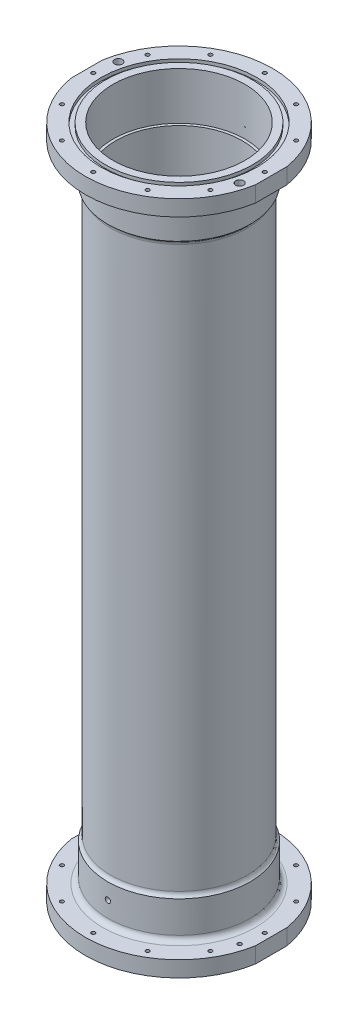
SolidWorks part; units mm, degrees
material "6061-T6 (SS)"
ref_plane "Front Plane" through (0, 0, 0) normal (0, 0, 1) x (1, 0, 0)
ref_plane "Top Plane" through (0, 0, 0) normal (0, 1, 0) x (1, 0, 0)
ref_plane "Right Plane" through (0, 0, 0) normal (1, 0, 0) x (0, 0, -1)
sketch "Sketch2" plane through (0, 0, 0) normal (0, 1, 0) x (1, 0, 0)
  circle A0 centre (0, 0) radius 38.1
  circle A1 centre (0, 0) radius 41.275
  dimension "D1" = 82.55
  dimension "D2" = 76.2
extrude "Base Cylinder" add sketch "Sketch2" along normal blind 406.4
sketch "Sketch3" plane through (0, 0, 0) normal (0, -1, 0) x (1, 0, 0)
  circle A0 centre (0, 0) radius 38.1
  circle A1 centre (0, 0) radius 56.3562
  dimension "D1" = 112.7125
extrude "Aft Flange" add sketch "Sketch3" against normal blind 9.525
sketch "Sketch34" plane through (0, 0, 0) normal (0, -1, 0) x (1, 0, 0)
  circle A0 centre (0, 0) radius 39.75
  dimension "D1" = 79.5
extrude "TemperatureInsert" cut sketch "Sketch34" against normal blind 28.575
sketch "Sketch6" plane through (0, 0, 0) normal (0, -1, 0) x (1, 0, 0)
  circle A0 centre (0, 0) radius 46.9011
  circle A1 centre (0, 0) radius 44.2849
  dimension "D1" = 93.8022
  dimension "D2" = 88.5698
extrude "Aft O-Ring" cut sketch "Sketch6" against normal blind 1.9812
sketch "Sketch33" plane through (0, 9.525, 0) normal (0, 1, 0) x (1, 0, 0)
  circle A0 centre (0, 0) radius 41.275
  circle A1 centre (0, 0) radius 42.8625
  dimension "D1" = 82.55
  dimension "D2" = 85.725
extrude "CriticalBoss" add sketch "Sketch33" along normal blind 22.225
sketch "Sketch For Bolt Holes" plane through (0, 0, 0) normal (0, -1, 0) x (1, 0, 0)
  circle A0 centre (-51.6255, 0) radius 1.5875
  circle A1 centre (-44.709, 25.8128) radius 1.5875
  circle A2 centre (-25.8128, 44.709) radius 1.5875
  circle A3 centre (0, 51.6255) radius 1.5875
  circle A4 centre (25.8127, 44.709) radius 1.5875
  circle A5 centre (44.709, 25.8128) radius 1.5875
  circle A6 centre (51.6255, 0) radius 1.5875
  circle A7 centre (44.709, -25.8127) radius 1.5875
  circle A8 centre (25.8128, -44.709) radius 1.5875
  circle A9 centre (0, -51.6255) radius 1.5875
  circle A10 centre (-25.8127, -44.709) radius 1.5875
  circle A11 centre (-44.709, -25.8128) radius 1.5875
  point P36 (0, 0)
  dimension "D2" = 3.175
  dimension "D1" = 51.6255
  dimension "D3" = 12
hole_wizard "Bolt Circle" positions "Sketch8" profile "Sketch9" hole size "#4-40" standard "ANSI Inch"
sketch "Sketch8" plane through (0, 0, 0) normal (0, -1, 0) x (-1, 0, 0)
  point P0 (-25.8127, -44.709)
  point P3 (-44.709, -25.8128)
  point P6 (-51.6255, 0)
  point P9 (-44.709, 25.8127)
  point P12 (-25.8128, 44.709)
  point P15 (0, 51.6255)
  point P18 (25.8127, 44.709)
  point P21 (44.709, 25.8128)
  point P24 (51.6255, 0)
  point P27 (44.709, -25.8128)
  point P30 (25.8128, -44.709)
  point P33 (0, -51.6255)
  point P36 (-25.8127, -44.709)
  point P38 (-44.709, -25.8128)
  point P40 (-51.6255, 0)
sketch "Sketch9" plane through (25.8127, 0, 44.709) normal (1, 0, 0) x (0, 0, -1)
  line L0 (0, 0) -> (0, 26.0792)
  line L1 (0, 26.0792) -> (1.1303, 25.4)
  line L2 (1.1303, 25.4) -> (1.1303, 0)
  line L5 (1.1303, 0) -> (0, 0)
  line L10 (0, 26.0792) -> (-1.1303, 25.4) construction
  line L11 (0, -6.35) -> (0, 107.95) construction
  dimension "Hole Dia." = 2.2606
  dimension "Hole Depth" = 25.4
  dimension "Drill Angle" = 118
fillet "CriticalBoss Flange" radius 3.175 2 edges at (0, 31.75, 41.275) (0, 9.525, -42.8625)
sketch "Dowel Hole Sketch" plane through (0, 0, 0) normal (0, -1, 0) x (1, 0, 0)
  line L0 (0, 0) -> (-51.6255, 0) construction
  line L1 (0, 0) -> (-49.8664, -13.3617) construction
  line L2 (0, 0) -> (0, -51.6255) construction
  line L3 (0, 0) -> (49.8664, 13.3617) construction
  circle A0 centre (0, 0) radius 51.6255
  circle A1 centre (-49.8664, -13.3617) radius 4.6172
  circle A2 centre (49.8664, 13.3617) radius 3.4532
  dimension "D1" = 15
hole_wizard "3/16 (0.1875) Press Dowel Hole1" positions "Sketch14" profile "Sketch12" hole size "3/16" standard "ANSI Inch"
sketch "Sketch14" plane through (0, 0, 0) normal (0, -1, 0) x (-1, 0, 0)
  point P0 (49.8664, 13.3617)
  point P3 (-49.8664, -13.3617)
sketch "Sketch12" plane through (-49.8664, 0, -13.3617) normal (1, 0, 0) x (0, 0, -1)
  line L0 (0, 0) -> (0, 7.7808)
  line L1 (0, 7.7808) -> (2.3812, 6.35)
  line L2 (2.3812, 6.35) -> (2.3812, 0)
  line L5 (2.3812, 0) -> (0, 0)
  line L10 (0, 7.7808) -> (-2.3813, 6.35) construction
  line L11 (0, -6.35) -> (0, 107.95) construction
  dimension "Hole Dia." = 4.7625
  dimension "Hole Depth" = 6.35
  dimension "Drill Angle" = 118
hole_wizard "3/32 (0.09375) Diameter Hole1" positions "Sketch19" profile "Sketch21" hole size "3/32" standard "ANSI Inch" end condition up to next
sketch "Sketch19" plane through (0, 0, 0) normal (0, -1, 0) x (-1, 0, 0)
  point P0 (-49.8664, -13.3617)
  point P3 (49.8664, 13.3617)
sketch "Sketch21" plane through (49.8664, 0, 13.3617) normal (1, 0, 0) x (0, 0, -1)
  line L0 (0, 0) -> (0, 398.6192)
  line L1 (0, 398.6192) -> (1.1906, 398.6192)
  line L2 (1.1906, 398.6192) -> (1.1906, 0)
  line L5 (1.1906, 0) -> (0, 0)
  line L11 (0, -6.35) -> (0, 107.95) construction
  dimension "Thru Hole Dia." = 2.3812
  dimension "Thru Hole Depth" = 398.6192
ref_plane "Hoop Mid-Plane" through (0, 203.2, 0) normal (0, 1, 0) x (1, 0, 0)
mirror "Forward Mirror BC and Pin" about plane through (0, 203.2, 0) normal (0, 1, 0) of "CriticalBoss Flange", "TemperatureInsert", "CriticalBoss", "Aft O-Ring", "3/16 (0.1875) Press Dowel Hole1", "3/32 (0.09375) Diameter Hole1", "Bolt Circle", "Aft Flange"
ref_plane "PressureTapHolePlane" [suppressed] through (0, 0, 42.8625) normal (0, 0, 1) x (1, 0, 0)
ref_plane "PressureTapHole2Plane" [suppressed] through (0, 0, -42.8625) normal (0, 0, 1) x (1, 0, 0)
sketch "Sketch35" plane through (0, 0, 42.8625) normal (0, 0, 1) x (1, 0, 0)
  line L0 (-56.3562, 0) -> (56.3562, 0) construction
  circle A0 centre (0, 22.225) radius 1.5875
  dimension "D1" = 22.225
  dimension "D2" = 3.175
extrude "Pressure Tap Aft Big" cut sketch "Sketch35" against normal blind 2.3813
sketch "Sketch41" plane through (0, 0, 40.4812) normal (0, 0, 1) x (1, 0, 0)
  circle A0 centre (0, 22.225) radius 0.1984
extrude "Pressure Tap Aft Small" cut sketch "Sketch41" against normal up to next
sketch "Sketch42" plane through (0, 0, -42.8625) normal (0, 0, 1) x (1, 0, 0)
  line L0 (56.3562, 406.4) -> (-56.3562, 406.4) construction
  circle A0 centre (0, 384.175) radius 1.5875
  dimension "D1" = 22.225
  dimension "D2" = 3.175
extrude "Pressure Tap Foreward Big" cut sketch "Sketch42" along normal blind 2.3813
sketch "Sketch43" plane through (0, 0, -40.4812) normal (0, 0, -1) x (-1, 0, 0)
  circle A0 centre (0, 384.175) radius 0.1984
  dimension "D1" = 0.3969
extrude "Pressure Tap Foreward Small" cut sketch "Sketch43" against normal up to next
sketch "Sketch44" plane through (0, 406.4, 0) normal (0, 1, 0) x (1, 0, 0)
  line L0 (0, -61.9919) -> (0, 61.9919) construction
  line L1 (55.5625, 11.3005) -> (57.15, 11.3005)
  line L2 (55.5625, 11.3005) -> (55.5625, -11.3005)
  line L3 (55.5625, -11.3005) -> (57.15, -11.3005)
  line L4 (57.15, 11.3005) -> (57.15, -11.3005)
  line L5 (55.5625, 11.3005) -> (57.15, -11.3005) construction
  line L6 (55.5625, -11.3005) -> (57.15, 11.3005) construction
  line L7 (-55.5625, -11.3005) -> (-57.15, -11.3005)
  line L8 (-57.15, 11.3005) -> (-57.15, -11.3005)
  line L9 (-55.5625, 11.3005) -> (-57.15, 11.3005)
  line L10 (-55.5625, 11.3005) -> (-55.5625, -11.3005)
  circle A0 centre (0, 0) radius 56.3562 construction
  point P0 (56.3562, 0)
  dimension "D1" = 1.5875
extrude "Mill Grips" cut sketch "Sketch44" against normal through all
